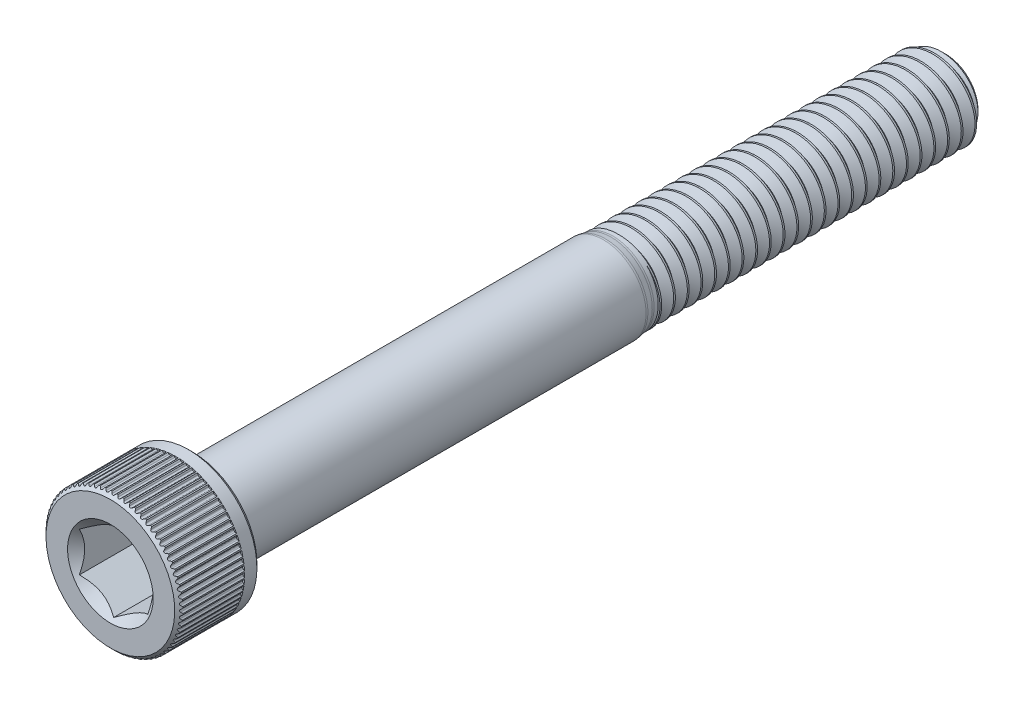
SolidWorks part; units mm, degrees
material "Alloy Steel"
ref_plane "Front Plane" through (0, 0, 0) normal (0, 0, 1) x (1, 0, 0)
ref_plane "Top Plane" through (0, 0, 0) normal (0, 1, 0) x (1, 0, 0)
ref_plane "Right Plane" through (0, 0, 0) normal (1, 0, 0) x (0, 0, -1)
sketch "Sketch1" plane through (0, 0, 0) normal (1, 0, 0) x (0, 0, -1)
  line L0 (-30.5, 0) -> (30.5, 0) construction
  line L1 (30.5, 0) -> (30.5, 2.3505) construction
  line L2 (30.5, 2.3505) -> (29.8505, 3) construction
  line L3 (29.8505, 3) -> (29.75, 3) construction
  line L4 (29.75, 3) -> (-24.5, 3) construction
  line L5 (-24.5, 3) -> (-24.5, 5) construction
  line L6 (-24.5, 5) -> (-30.5, 5) construction
  line L7 (-30.5, 5) -> (-30.5, 0) construction
  line L8 (30.5, 2.3505) -> (30.5, 3) construction
  line L9 (30.4375, 3.1083) -> (30.9375, 2.2422) construction
  line L10 (30.9375, 2.2422) -> (31.4375, 3.1083) construction
  line L11 (31.4375, 3.1083) -> (30.4375, 3.1083) construction
  line L12 (30.9375, 3.1083) -> (30.9375, 3) construction
  line L13 (30.9375, 2.2422) -> (30.9375, 2.3505) construction
  line L14 (30.875, 2.3505) -> (31, 2.3505) construction
  line L15 (30.5, 3) -> (31.375, 3) construction
  line L16 (30.4688, 3.0541) -> (31.4062, 3.0541) construction
  line L17 (30.5, 0) -> (30.5, -3) construction
  line L18 (-24.8, 5) -> (-24.5, 4.7) construction
  line L19 (-30.2, 5) -> (-30.5, 4.7) construction
  line L20 (-24.5, 3) -> (-24.5, 0) construction
  line L21 (-24.5, 1.5) -> (-6.1667, 1.5) construction
  line L22 (-6.1667, 1.5) -> (12.1667, 1.5) construction
  line L23 (12.1667, 1.5) -> (30.5, 1.5) construction
  line L24 (-6.1667, 1.5) -> (-6.1667, 3) construction
  line L25 (-6.1667, 3) -> (-6.1667, 5) construction
  line L26 (12.1667, 1.5) -> (12.1667, 5) construction
  point P0 (-30.5, 2.5)
  point P3 (28, 3)
  point P4 (0, 0)
  point P18 (12.1667, 3)
  point P22 (30.9375, 2.3505)
  point P24 (29.75, 3)
  point P25 (30.9375, 3)
  point P28 (30.9375, 3.0541)
  point P29 (28, -3)
  point P30 (-6.1667, 3)
  point P31 (-27.5, 5)
  point P37 (-25.55, 5)
  point P38 (-30.05, 5)
  point P45 (-6.1667, 1.5)
  point P46 (12.1667, 1.5)
  point P49 (6.5, 3)
  dimension "D1" = 45
  dimension "D2" = 0.125
  dimension "D7" = 0.3
  dimension "D8" = 0.3
  dimension "D9" = 0.3
  dimension "D10" = 0.15
  dimension "D11" = 0.75
  dimension "Drive Size" = 5
  dimension "Head Diameter" = 10
  dimension "Head Height" = 6
  dimension "Thread Pitch" = 1
  dimension "Thread Size" = 6
  dimension "Length" = 55
  dimension "D12" = 0.75
  dimension "D4" = 2.5
  dimension "Minimum Thread Length" = 24
  dimension "D3" = 31
sketch "Sketch2" plane through (0, 0, 0) normal (1, 0, 0) x (0, 0, -1)
  line L0 (-30.5, 0) -> (-30.5, 4.7)
  line L1 (-30.2, 5) -> (-24.8, 5)
  line L2 (-24.5, 4.7) -> (-24.5, 3.4083)
  line L4 (29.8505, 3) -> (30.5, 2.3505)
  line L5 (30.5, 2.3505) -> (30.5, 0)
  line L6 (-24.5, 5) -> (-30.5, 5) construction
  line L7 (30.5, 0) -> (-30.5, 0)
  line L8 (-30.2, 5) -> (-30.5, 4.7) construction
  line L10 (-30.2, 5) -> (-30.5, 4.7)
  line L14 (-24.8, 5) -> (-24.5, 4.7) construction
  line L16 (-24.8, 5) -> (-24.5, 4.7)
  line L17 (-24.5, 3) -> (-24.5, 5) construction
  line L18 (-24.2, 3.1083) -> (5.5069, 3.1083)
  line L19 (6.1989, 3) -> (29.8505, 3)
  line L20 (29.75, 3) -> (-24.5, 3) construction
  line L21 (5.6532, 3.0938) -> (6.0526, 3.0144)
  line L22 (31.4375, 3.1083) -> (30.4375, 3.1083) construction
  arc A1 (-24.5, 3.4083) -> (-24.2, 3.1083) centre (-24.2, 3.4083) ccw
  arc A2 (5.5069, 3.1083) -> (5.6532, 3.0938) centre (5.5069, 2.3583) cw
  arc A3 (6.0526, 3.0144) -> (6.1989, 3) centre (6.1989, 3.75) ccw
  point P39 (6.125, 3)
  dimension "D3" = 0.3
  dimension "D6" = 0.75
  dimension "D4" = 11.25
  dimension "D5" = 0.375
revolve "Revolve1" add sketch "Sketch2" angle 360 about L7
sketch "Sketch3" plane through (0, 0, 30.5) normal (0, 0, 1) x (1, 0, 0)
  line L1 (2.5, -1.4434) -> (2.5, 1.4434)
  line L2 (2.5, 1.4434) -> (0, 2.8868)
  line L3 (0, 2.8868) -> (-2.5, 1.4434)
  line L4 (-2.5, 1.4434) -> (-2.5, -1.4434)
  line L5 (-2.5, -1.4434) -> (0, -2.8868)
  line L6 (0, -2.8868) -> (2.5, -1.4434)
  circle A0 centre (0, 0) radius 2.5 construction
  circle A1 centre (0, 0) radius 5 construction
  circle A2 centre (0, 0) radius 5 construction
  circle A3 centre (0, 0) radius 2.8868 construction
extrude "Cut-Extrude1" cut sketch "Sketch3" against normal offset from surface (5 mm away) 1 up to face at (0, 4.7, 24.5)
sketch "Sketch4" plane through (0, 0, 30.5) normal (0, 0, 1) x (1, 0, 0)
  circle A0 centre (0, 0) radius 3.125
  dimension "D1" = 6.25
extrude "Cut-Extrude2" cut sketch "Sketch4" against normal up to vertex (3 mm away) draft 45 up to point (0, 5, 27.5)
sketch "Sketch11" plane through (0, 0, 0) normal (1, 0, 0) x (0, 0, -1)
  line L0 (-30.5, 0) -> (30.5, 0) construction
  line L1 (-30.5, 0) -> (30.5, 0) construction
  line L2 (-21.7875, 0) -> (-21.7875, 3) construction
  line L3 (29.75, 3) -> (-24.5, 3) construction
  line L4 (2.7944, 0) -> (2.7944, 3) construction
  point P2 (-21.7875, 0)
  point P3 (2.7944, 0)
  dimension "D1" = 2.7125
  dimension "D2" = 2.7125
sketch "Sketch6" plane through (0, 0, -30.5) normal (0, 0, -1) x (-1, 0, 0)
  circle A0 centre (0, 0) radius 3
curve "Helix/Spiral1" pitch 1 height 25 radius 3 centre (0, 0, -30.5) axis (0, 0, 1) start towards (0, 1, 0)
sketch "Sketch10" plane through (0, 0, 0) normal (1, 0, 0) x (0, 0, -1)
  line L0 (6.5, -3) -> (6.5, 3)
  line L2 (-30.5, 0) -> (30.5, 0) construction
  point P3 (6.5, 0)
split "Split1" trim tools "Sketch10" bodies to split 106 resulting bodies 114 115
sketch "Sketch7" plane through (0, 0, 0) normal (1, 0, 0) x (0, 0, -1)
  line L0 (30.4688, 3.0541) -> (31.4062, 3.0541)
  line L1 (31.4062, 3.0541) -> (31, 2.3505)
  line L2 (31, 2.3505) -> (30.875, 2.3505)
  line L3 (30.875, 2.3505) -> (30.4688, 3.0541)
sweep "Cut-Sweep1" cut profiles "Sketch7" path "Helix/Spiral1" align with end faces yes
sketch "Sketch8" plane through (0, 0, 0) normal (1, 0, 0) x (0, 0, -1)
  line L0 (-24.5, 0) -> (-24.5, 3)
  line L2 (-24.5, 3) -> (6.5, 3)
  line L4 (6.5, 3) -> (8.2321, 0)
  line L5 (8.2321, 0) -> (-24.5, 0)
  line L6 (29.75, 3) -> (-24.5, 3) construction
  line L7 (-30.5, 0) -> (30.5, 0) construction
  dimension "D1" = 60
  dimension "D2" = 24
revolve "Revolve2" add sketch "Sketch8" angle 360 about L5
ref_plane "Plane1" through (0, 0, 30.5) normal (0, 0, 1) x (1, 0, 0)
sketch "Sketch12" plane through (0, 0, 30.5) normal (0, 0, 1) x (1, 0, 0)
  line L0 (0, 0) -> (0.1745, 4.997) construction
  line L1 (0, 0) -> (-0.1745, 4.997) construction
  line L2 (0, 5.125) -> (0, 4.875) construction
  line L3 (-0.3025, 5.125) -> (-0.0897, 4.9122)
  line L4 (0.0897, 4.9122) -> (0.3025, 5.125)
  line L5 (0.3025, 5.125) -> (-0.3025, 5.125)
  circle A0 centre (0, 0) radius 5 construction
  arc A1 (-0.0897, 4.9122) -> (0.0897, 4.9122) centre (0, 5.0019) ccw
  point P12 (0, 5)
  point P14 (0, 5.125)
  dimension "D2" = 0.125
extrude "Cut-Extrude3" cut sketch "Sketch12" against normal blind 4.8
pattern_circular "CirPattern1" count 72 over 360 about axis through (0, 0, 30.5) along (0, 0, -1) of "Cut-Extrude3"
equation "\"D2@Sketch1\" = \"Thread Pitch@Sketch1\" / 8"
equation "\"D4@Helix/Spiral1\" = \"Thread Pitch@Sketch1\""
equation "\"D7@Sketch1\" = \"Head Height@Sketch1\" * .05"
equation "\"D8@Sketch1\"=\"D7@Sketch1\""
equation "\"D9@Sketch1\"=\"D7@Sketch1\""
equation "\"D10@Sketch1\"=\"D7@Sketch1\"/2"
equation "\"D11@Sketch1\"=\"D10@Sketch1\"*5"
equation "\"D4@Sketch1\"=\"Thread Pitch@Sketch1\"*2.5"
equation "\"D12@Sketch1\"=\"Thread Pitch@Sketch1\"*.75"
equation "\"D3@Helix/Spiral1\"=\"Minimum Thread Length@Sketch1\"+\"Thread Pitch@Sketch1\""
equation "\"D2@Sketch8\"=\"Minimum Thread Length@Sketch1\""
equation "\"D3@Sketch2\"=\"Thread Size@Sketch1\"*0.05"
equation "\"D5@Sketch2\"=\"D12@Sketch1\"*0.5"
equation "\"D6@Sketch2\"=\"Thread Size@Sketch1\"*0.125"
equation "\"D1@Sketch11\"=(\"Length@Sketch1\"-\"Minimum Thread Length@Sketch1\")*0.0875"
equation "\"D2@Sketch11\"=\"D1@Sketch11\""
equation "\"D1@Sketch4\"=\"Drive Size@Sketch1\"*1.25"
equation "\"D2@Sketch12\"=\"Head Diameter@Sketch1\"*.0125"
equation "\"D1@Cut-Extrude3\"=\"Head Height@Sketch1\"*.8"
equation "\"D1@CirPattern1\"=\"D3@CirPattern1\"/(1.25*\"D1@Sketch12\")"
